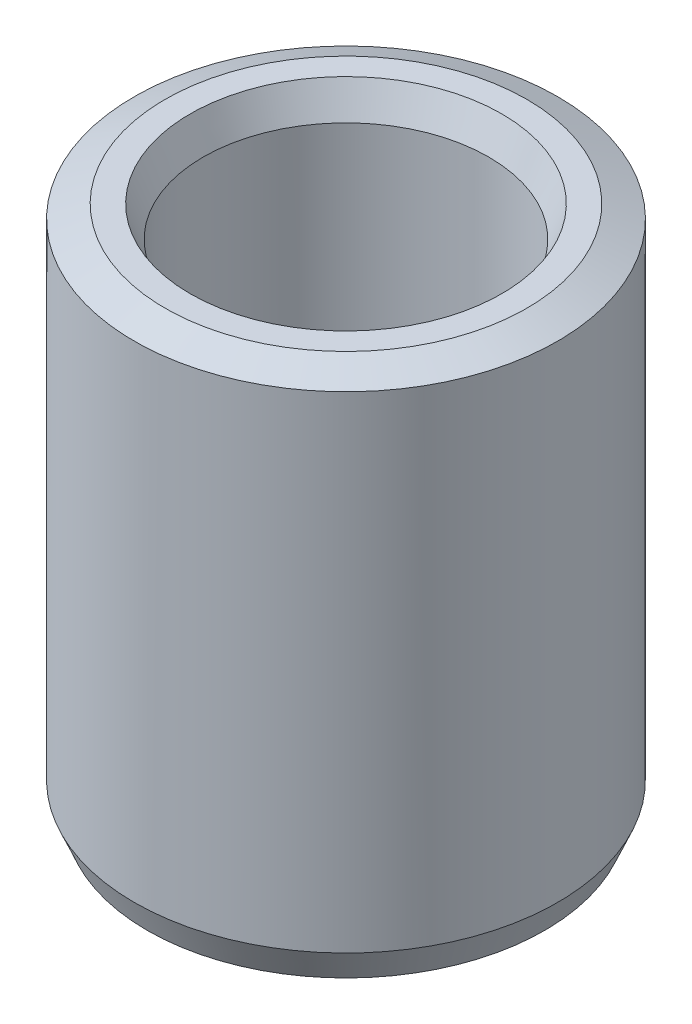
SolidWorks part; units mm, degrees
ref_plane "Front Plane" through (0, 0, 0) normal (0, 0, 1) x (1, 0, 0)
ref_plane "Top Plane" through (0, 0, 0) normal (0, 1, 0) x (1, 0, 0)
ref_plane "Right Plane" through (0, 0, 0) normal (1, 0, 0) x (0, 0, -1)
sketch "Sketch1" plane through (0, 0, 0) normal (0, 1, 0) x (1, 0, 0)
  circle A0 centre (0, 0) radius 55
  dimension "SLEEVE_OD" = 110
extrude "Boss-Extrude1" add sketch "Sketch1" along normal blind 137.6678
sketch "Sketch2" plane through (0, 0, 0) normal (0, 1, 0) x (1, 0, 0)
  circle A0 centre (0, 0) radius 37.0779
  dimension "BORE_D" = 74.1558
extrude "Cut-Extrude1" cut sketch "Sketch2" along normal through all
chamfer "Chamfer1" distance 3.3945 angle 67.035 4 edges at (0, 137.6678, 37.0779) (0, 0, 37.0779) (0, 0, 55) (0, 137.6678, 55) first distance on face at (0, 137.6678, 37.0779) first distance on face at (0, 0, 37.0779) first distance on face at (0, 137.6678, 55)
